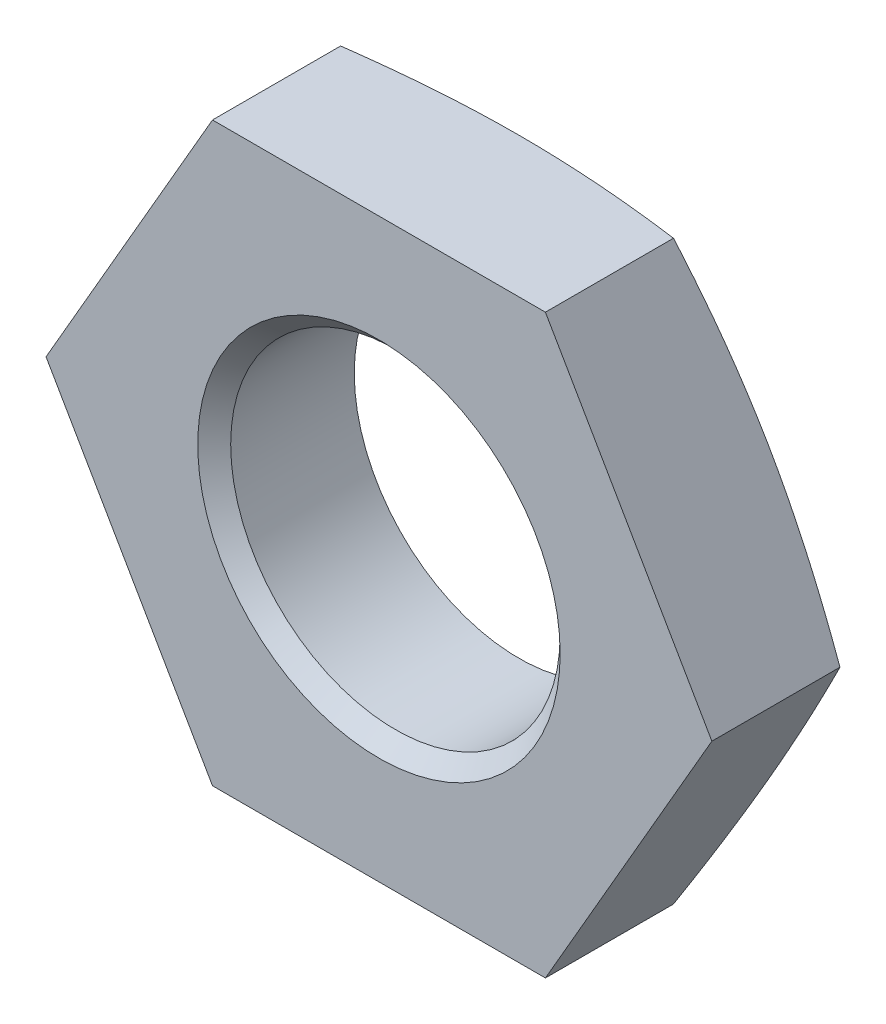
SolidWorks part; units mm, degrees
ref_plane "Front" through (0, 0, 0) normal (0, 0, 1) x (1, 0, 0)
ref_plane "Top" through (0, 0, 0) normal (0, 1, 0) x (1, 0, 0)
ref_plane "Right" through (0, 0, 0) normal (1, 0, 0) x (0, 0, -1)
sketch "Sketch1" plane through (0, 0, 0) normal (0, 0, 1) x (1, 0, 0)
  line L1 (2.0207, -3.5) -> (4.0415, 0)
  line L2 (4.0415, 0) -> (2.0207, 3.5)
  line L3 (2.0207, 3.5) -> (-2.0207, 3.5)
  line L4 (-2.0207, 3.5) -> (-4.0415, 0)
  line L5 (-4.0415, 0) -> (-2.0207, -3.5)
  line L6 (-2.0207, -3.5) -> (2.0207, -3.5)
  circle A0 centre (0, 0) radius 3.5 construction
  circle A1 centre (0, 0) radius 2
extrude "BaseNut" add sketch "Sketch1" against normal blind 1.7
cosmetic thread "ThreadCosmetic1" [suppressed] parameters "D2"=4.5
sketch "Sketch2" plane through (0, 0, 0) normal (0, 1, 0) x (1, 0, 0)
  line L0 (-4.0415, 1.7) -> (-3.5, 1.7)
  line L2 (-3.5, 1.7) -> (-4.0415, 1.5549)
  line L3 (-4.0415, 1.5549) -> (-4.0415, 1.7)
  line L4 (0, 3.3759) -> (0, -9.8171) construction
  line L6 (-9.7712, 0.85) -> (9.8853, 0.85) construction
  dimension "D2" = 0.85
revolve "Double-Chamfer" cut sketch "Sketch2" angle 360 about L4
chamfer "Chamfer1" distance 0.2 angle 45 1 edges at (2, 0, 0)
sketch "Sketch3" plane through (0, 0, 0) normal (0, 1, 0) x (1, 0, 0)
  line L0 (0, 2.7394) -> (0, -0.894) construction
  line L1 (1.75, 0.325) -> (2, 0.325)
  line L2 (2, 0.325) -> (2.2165, 0.2)
  line L3 (2.2165, 0.2) -> (2, 0.075)
  line L4 (2, 0.075) -> (1.75, 0.075)
  line L5 (1.75, 0.075) -> (1.75, 0.325)
  line L6 (2, 0.2) -> (-2, 0.2) construction
  dimension "D1" = 0.25
revolve "Cut-Revolve10" [suppressed] cut sketch "Sketch3" angle 360 about L0
pattern_linear "LPattern10" [suppressed] count 5 spacing 0.3 along (0, 0, -1) of bodies 103
equation "\"dw@Sketch2\" = \"s@Sketch1\""
equation "\"D2@Sketch2\" = \"m@BaseNut\" / 2"
equation "\"D1@Chamfer1\" = \"D@Sketch1\" / 20"
equation "\"D2@Sketch3\" = \"D@Sketch1\""
equation "\"D1@Sketch3\" = (  \"D2@ThreadCosmetic1\" - \"D@Sketch1\" )  / 2"
equation "\"D3@LPattern10\" = \"D1@Sketch3\" * 1.2"
equation "\"D1@LPattern10\" = (  \"m@BaseNut\"  - \"D1@Chamfer1\")  / \"D3@LPattern10\""
